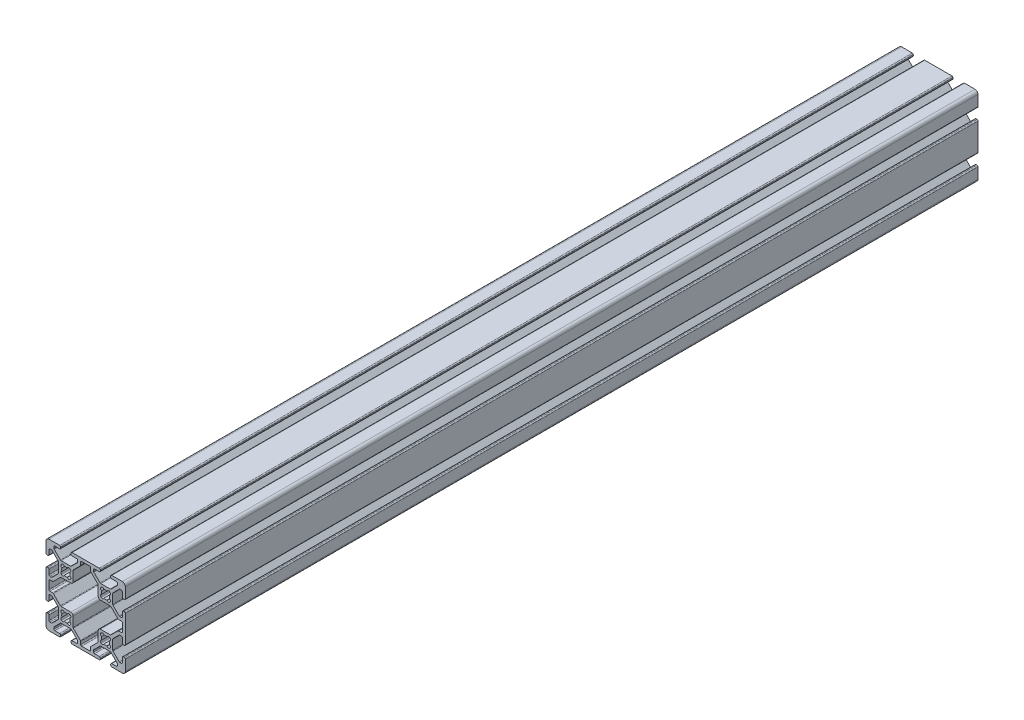
SolidWorks part; units mm, degrees
material "6105-T5 Aluminum"
ref_plane "Front Plane" through (0, 0, 0) normal (0, 0, 1) x (1, 0, 0)
ref_plane "Top Plane" through (0, 0, 0) normal (0, 1, 0) x (1, 0, 0)
ref_plane "Right Plane" through (0, 0, 0) normal (1, 0, 0) x (0, 0, -1)
sketch "Sketch1" plane through (0, 0, 0) normal (0, 0, 1) x (1, 0, 0)
  line L0 (-2.1249, 17.6955) -> (-2.3045, 17.8751)
  line L1 (-2.3045, 22.1249) -> (-2.1249, 22.3045)
  line L2 (2.1249, 22.3045) -> (2.3045, 22.1249)
  line L3 (2.3045, 17.8751) -> (2.1249, 17.6955)
  line L4 (-22.1249, 17.6955) -> (-22.3045, 17.8751)
  line L5 (-22.3045, 22.1249) -> (-22.1249, 22.3045)
  line L6 (-17.8751, 22.3045) -> (-17.6955, 22.1249)
  line L7 (-17.6955, 17.8751) -> (-17.8751, 17.6955)
  line L8 (-2.1249, -2.3045) -> (-2.3045, -2.1249)
  line L9 (-2.3045, 2.1249) -> (-2.1249, 2.3045)
  line L10 (2.1249, 2.3045) -> (2.3045, 2.1249)
  line L11 (2.3045, -2.1249) -> (2.1249, -2.3045)
  line L12 (-12.505, -7.992) -> (-12.505, -6.6448)
  line L13 (-12.6538, -6.2856) -> (-16.1962, -2.7431)
  line L14 (-16.345, -2.3839) -> (-16.345, 2.512)
  line L15 (-17.488, 3.655) -> (-22.3839, 3.655)
  line L16 (-22.7431, 3.8038) -> (-26.2856, 7.3462)
  line L17 (-26.6448, 7.495) -> (-27.992, 7.495)
  line L18 (-28.5, 8.003) -> (-28.5, 11.997)
  line L19 (-27.992, 12.505) -> (-26.6448, 12.505)
  line L20 (-26.2856, 12.6538) -> (-22.7431, 16.1962)
  line L21 (-22.3839, 16.345) -> (-17.488, 16.345)
  line L22 (-16.345, 17.488) -> (-16.345, 22.3839)
  line L23 (-16.1962, 22.7431) -> (-12.6538, 26.2856)
  line L24 (-12.505, 26.6448) -> (-12.505, 27.992)
  line L25 (-11.997, 28.5) -> (-8.003, 28.5)
  line L26 (-7.495, 27.992) -> (-7.495, 26.6448)
  line L27 (-7.3462, 26.2856) -> (-3.8038, 22.7431)
  line L28 (-3.655, 22.3839) -> (-3.655, 17.488)
  line L29 (-2.512, 16.345) -> (2.3839, 16.345)
  line L30 (2.7431, 16.1962) -> (6.2856, 12.6538)
  line L31 (6.6448, 12.505) -> (7.992, 12.505)
  line L32 (8.5, 11.997) -> (8.5, 8.003)
  line L33 (7.992, 7.495) -> (6.6448, 7.495)
  line L34 (6.2856, 7.3462) -> (2.7431, 3.8038)
  line L35 (2.3839, 3.655) -> (-2.512, 3.655)
  line L36 (-3.655, 2.512) -> (-3.655, -2.3839)
  line L37 (-3.8038, -2.7431) -> (-7.3462, -6.2856)
  line L38 (-7.495, -6.6448) -> (-7.495, -7.992)
  line L39 (-8.003, -8.5) -> (-11.997, -8.5)
  line L40 (-22.1249, -2.3045) -> (-22.3045, -2.1249)
  line L41 (-22.3045, 2.1249) -> (-22.1249, 2.3045)
  line L42 (-17.8751, 2.3045) -> (-17.6955, 2.1249)
  line L43 (-17.6955, -2.1249) -> (-17.8751, -2.3045)
  line L44 (-22.3839, -3.655) -> (-17.6161, -3.655)
  line L45 (-17.2569, -3.8038) -> (-14.1538, -6.9069)
  line L46 (-14.005, -7.2661) -> (-14.005, -7.992)
  line L47 (-14.513, -8.5) -> (-16.862, -8.5)
  line L48 (-17.37, -9.008) -> (-17.37, -9.492)
  line L49 (-16.862, -10) -> (-3.138, -10)
  line L50 (-2.63, -9.492) -> (-2.63, -9.008)
  line L51 (-3.138, -8.5) -> (-5.487, -8.5)
  line L52 (-5.995, -7.992) -> (-5.995, -7.2661)
  line L53 (-5.8462, -6.9069) -> (-2.7431, -3.8038)
  line L54 (-2.3839, -3.655) -> (2.3839, -3.655)
  line L55 (2.7431, -3.8038) -> (5.8462, -6.9069)
  line L56 (5.995, -7.2661) -> (5.995, -7.992)
  line L57 (5.487, -8.5) -> (3.138, -8.5)
  line L58 (2.63, -9.008) -> (2.63, -9.492)
  line L59 (3.138, -10) -> (8.5, -10)
  line L60 (10, -8.5) -> (10, -3.138)
  line L61 (9.492, -2.63) -> (9.008, -2.63)
  line L62 (8.5, -3.138) -> (8.5, -5.487)
  line L63 (7.992, -5.995) -> (7.2661, -5.995)
  line L64 (6.9069, -5.8462) -> (3.8038, -2.7431)
  line L65 (3.655, -2.3839) -> (3.655, 2.3839)
  line L66 (3.8038, 2.7431) -> (6.9069, 5.8462)
  line L67 (7.2661, 5.995) -> (7.992, 5.995)
  line L68 (8.5, 5.487) -> (8.5, 3.138)
  line L69 (9.008, 2.63) -> (9.492, 2.63)
  line L70 (10, 3.138) -> (10, 16.862)
  line L71 (9.492, 17.37) -> (9.008, 17.37)
  line L72 (8.5, 16.862) -> (8.5, 14.513)
  line L73 (7.992, 14.005) -> (7.2661, 14.005)
  line L74 (6.9069, 14.1538) -> (3.8038, 17.2569)
  line L75 (3.655, 17.6161) -> (3.655, 22.3839)
  line L76 (3.8038, 22.7431) -> (6.9069, 25.8462)
  line L77 (7.2661, 25.995) -> (7.992, 25.995)
  line L78 (8.5, 25.487) -> (8.5, 23.138)
  line L79 (9.008, 22.63) -> (9.492, 22.63)
  line L80 (10, 23.138) -> (10, 28.5)
  line L81 (8.5, 30) -> (3.138, 30)
  line L82 (2.63, 29.492) -> (2.63, 29.008)
  line L83 (3.138, 28.5) -> (5.487, 28.5)
  line L84 (5.995, 27.992) -> (5.995, 27.2661)
  line L85 (5.8462, 26.9069) -> (2.7431, 23.8038)
  line L86 (2.3839, 23.655) -> (-2.3839, 23.655)
  line L87 (-2.7431, 23.8038) -> (-5.8462, 26.9069)
  line L88 (-5.995, 27.2661) -> (-5.995, 27.992)
  line L89 (-5.487, 28.5) -> (-3.138, 28.5)
  line L90 (-2.63, 29.008) -> (-2.63, 29.492)
  line L91 (-3.138, 30) -> (-16.862, 30)
  line L92 (-17.37, 29.492) -> (-17.37, 29.008)
  line L93 (-16.862, 28.5) -> (-14.513, 28.5)
  line L94 (-14.005, 27.992) -> (-14.005, 27.2661)
  line L95 (-14.1538, 26.9069) -> (-17.2569, 23.8038)
  line L96 (-17.6161, 23.655) -> (-22.3839, 23.655)
  line L97 (-22.7431, 23.8038) -> (-25.8462, 26.9069)
  line L98 (-25.995, 27.2661) -> (-25.995, 27.992)
  line L99 (-25.487, 28.5) -> (-23.138, 28.5)
  line L100 (-22.63, 29.008) -> (-22.63, 29.492)
  line L101 (-23.138, 30) -> (-28.5, 30)
  line L102 (-30, 28.5) -> (-30, 23.138)
  line L103 (-29.492, 22.63) -> (-29.008, 22.63)
  line L104 (-28.5, 23.138) -> (-28.5, 25.487)
  line L105 (-27.992, 25.995) -> (-27.2661, 25.995)
  line L106 (-26.9069, 25.8462) -> (-23.8038, 22.7431)
  line L107 (-23.655, 22.3839) -> (-23.655, 17.6161)
  line L108 (-23.8038, 17.2569) -> (-26.9069, 14.1538)
  line L109 (-27.2661, 14.005) -> (-27.992, 14.005)
  line L110 (-28.5, 14.513) -> (-28.5, 16.862)
  line L111 (-29.008, 17.37) -> (-29.492, 17.37)
  line L112 (-30, 16.862) -> (-30, 3.138)
  line L113 (-29.492, 2.63) -> (-29.008, 2.63)
  line L114 (-28.5, 3.138) -> (-28.5, 5.487)
  line L115 (-27.992, 5.995) -> (-27.2661, 5.995)
  line L116 (-26.9069, 5.8462) -> (-23.8038, 2.7431)
  line L117 (-23.655, 2.3839) -> (-23.655, -2.3839)
  line L118 (-23.8038, -2.7431) -> (-26.9069, -5.8462)
  line L119 (-27.2661, -5.995) -> (-27.992, -5.995)
  line L120 (-28.5, -5.487) -> (-28.5, -3.138)
  line L121 (-29.008, -2.63) -> (-29.492, -2.63)
  line L122 (-30, -3.138) -> (-30, -8.5)
  line L123 (-28.5, -10) -> (-23.138, -10)
  line L124 (-22.63, -9.492) -> (-22.63, -9.008)
  line L125 (-23.138, -8.5) -> (-25.487, -8.5)
  line L126 (-25.995, -7.992) -> (-25.995, -7.2661)
  line L127 (-25.8462, -6.9069) -> (-22.7431, -3.8038)
  arc A0 (-1.9351, 19.196) -> (-2.3045, 17.8751) centre (-1.748, 18.4316) ccw
  arc A1 (-1.9351, 20.804) -> (-1.9351, 19.196) centre (0, 20) ccw
  arc A2 (-2.3045, 22.1249) -> (-1.9351, 20.804) centre (-1.748, 21.5684) ccw
  arc A3 (-0.804, 21.9351) -> (-2.1249, 22.3045) centre (-1.5684, 21.748) ccw
  arc A4 (0.804, 21.9351) -> (-0.804, 21.9351) centre (0, 20) ccw
  arc A5 (2.1249, 22.3045) -> (0.804, 21.9351) centre (1.5684, 21.748) ccw
  arc A6 (1.9351, 20.804) -> (2.3045, 22.1249) centre (1.748, 21.5684) ccw
  arc A7 (1.9351, 19.196) -> (1.9351, 20.804) centre (0, 20) ccw
  arc A8 (2.3045, 17.8751) -> (1.9351, 19.196) centre (1.748, 18.4316) ccw
  arc A9 (0.804, 18.0649) -> (2.1249, 17.6955) centre (1.5684, 18.252) ccw
  arc A10 (-0.804, 18.0649) -> (0.804, 18.0649) centre (0, 20) ccw
  arc A11 (-2.1249, 17.6955) -> (-0.804, 18.0649) centre (-1.5684, 18.252) ccw
  arc A12 (-21.9351, 19.196) -> (-22.3045, 17.8751) centre (-21.748, 18.4316) ccw
  arc A13 (-21.9351, 20.804) -> (-21.9351, 19.196) centre (-20, 20) ccw
  arc A14 (-22.3045, 22.1249) -> (-21.9351, 20.804) centre (-21.748, 21.5684) ccw
  arc A15 (-20.804, 21.9351) -> (-22.1249, 22.3045) centre (-21.5684, 21.748) ccw
  arc A16 (-19.196, 21.9351) -> (-20.804, 21.9351) centre (-20, 20) ccw
  arc A17 (-17.8751, 22.3045) -> (-19.196, 21.9351) centre (-18.4316, 21.748) ccw
  arc A18 (-18.0649, 20.804) -> (-17.6955, 22.1249) centre (-18.252, 21.5684) ccw
  arc A19 (-18.0649, 19.196) -> (-18.0649, 20.804) centre (-20, 20) ccw
  arc A20 (-17.6955, 17.8751) -> (-18.0649, 19.196) centre (-18.252, 18.4316) ccw
  arc A21 (-19.196, 18.0649) -> (-17.8751, 17.6955) centre (-18.4316, 18.252) ccw
  arc A22 (-20.804, 18.0649) -> (-19.196, 18.0649) centre (-20, 20) ccw
  arc A23 (-22.1249, 17.6955) -> (-20.804, 18.0649) centre (-21.5684, 18.252) ccw
  arc A24 (-1.9351, -0.804) -> (-2.3045, -2.1249) centre (-1.748, -1.5684) ccw
  arc A25 (-1.9351, 0.804) -> (-1.9351, -0.804) centre (0, 0) ccw
  arc A26 (-2.3045, 2.1249) -> (-1.9351, 0.804) centre (-1.748, 1.5684) ccw
  arc A27 (-0.804, 1.9351) -> (-2.1249, 2.3045) centre (-1.5684, 1.748) ccw
  arc A28 (0.804, 1.9351) -> (-0.804, 1.9351) centre (0, 0) ccw
  arc A29 (2.1249, 2.3045) -> (0.804, 1.9351) centre (1.5684, 1.748) ccw
  arc A30 (1.9351, 0.804) -> (2.3045, 2.1249) centre (1.748, 1.5684) ccw
  arc A31 (1.9351, -0.804) -> (1.9351, 0.804) centre (0, 0) ccw
  arc A32 (2.3045, -2.1249) -> (1.9351, -0.804) centre (1.748, -1.5684) ccw
  arc A33 (0.804, -1.9351) -> (2.1249, -2.3045) centre (1.5684, -1.748) ccw
  arc A34 (-0.804, -1.9351) -> (0.804, -1.9351) centre (0, 0) ccw
  arc A35 (-2.1249, -2.3045) -> (-0.804, -1.9351) centre (-1.5684, -1.748) ccw
  arc A36 (-12.505, -7.992) -> (-11.997, -8.5) centre (-11.997, -7.992) ccw
  arc A37 (-12.505, -6.6448) -> (-12.6538, -6.2856) centre (-13.013, -6.6448) ccw
  arc A38 (-16.345, -2.3839) -> (-16.1962, -2.7431) centre (-15.837, -2.3839) ccw
  arc A39 (-16.345, 2.512) -> (-17.488, 3.655) centre (-17.488, 2.512) ccw
  arc A40 (-22.7431, 3.8038) -> (-22.3839, 3.655) centre (-22.3839, 4.163) ccw
  arc A41 (-26.2856, 7.3462) -> (-26.6448, 7.495) centre (-26.6448, 6.987) ccw
  arc A42 (-28.5, 8.003) -> (-27.992, 7.495) centre (-27.992, 8.003) ccw
  arc A43 (-27.992, 12.505) -> (-28.5, 11.997) centre (-27.992, 11.997) ccw
  arc A44 (-26.6448, 12.505) -> (-26.2856, 12.6538) centre (-26.6448, 13.013) ccw
  arc A45 (-22.3839, 16.345) -> (-22.7431, 16.1962) centre (-22.3839, 15.837) ccw
  arc A46 (-17.488, 16.345) -> (-16.345, 17.488) centre (-17.488, 17.488) ccw
  arc A47 (-16.1962, 22.7431) -> (-16.345, 22.3839) centre (-15.837, 22.3839) ccw
  arc A48 (-12.6538, 26.2856) -> (-12.505, 26.6448) centre (-13.013, 26.6448) ccw
  arc A49 (-11.997, 28.5) -> (-12.505, 27.992) centre (-11.997, 27.992) ccw
  arc A50 (-7.495, 27.992) -> (-8.003, 28.5) centre (-8.003, 27.992) ccw
  arc A51 (-7.495, 26.6448) -> (-7.3462, 26.2856) centre (-6.987, 26.6448) ccw
  arc A52 (-3.655, 22.3839) -> (-3.8038, 22.7431) centre (-4.163, 22.3839) ccw
  arc A53 (-3.655, 17.488) -> (-2.512, 16.345) centre (-2.512, 17.488) ccw
  arc A54 (2.7431, 16.1962) -> (2.3839, 16.345) centre (2.3839, 15.837) ccw
  arc A55 (6.2856, 12.6538) -> (6.6448, 12.505) centre (6.6448, 13.013) ccw
  arc A56 (8.5, 11.997) -> (7.992, 12.505) centre (7.992, 11.997) ccw
  arc A57 (7.992, 7.495) -> (8.5, 8.003) centre (7.992, 8.003) ccw
  arc A58 (6.6448, 7.495) -> (6.2856, 7.3462) centre (6.6448, 6.987) ccw
  arc A59 (2.3839, 3.655) -> (2.7431, 3.8038) centre (2.3839, 4.163) ccw
  arc A60 (-2.512, 3.655) -> (-3.655, 2.512) centre (-2.512, 2.512) ccw
  arc A61 (-3.8038, -2.7431) -> (-3.655, -2.3839) centre (-4.163, -2.3839) ccw
  arc A62 (-7.3462, -6.2856) -> (-7.495, -6.6448) centre (-6.987, -6.6448) ccw
  arc A63 (-8.003, -8.5) -> (-7.495, -7.992) centre (-8.003, -7.992) ccw
  arc A64 (-21.9351, -0.804) -> (-22.3045, -2.1249) centre (-21.748, -1.5684) ccw
  arc A65 (-21.9351, 0.804) -> (-21.9351, -0.804) centre (-20, 0) ccw
  arc A66 (-22.3045, 2.1249) -> (-21.9351, 0.804) centre (-21.748, 1.5684) ccw
  arc A67 (-20.804, 1.9351) -> (-22.1249, 2.3045) centre (-21.5684, 1.748) ccw
  arc A68 (-19.196, 1.9351) -> (-20.804, 1.9351) centre (-20, 0) ccw
  arc A69 (-17.8751, 2.3045) -> (-19.196, 1.9351) centre (-18.4316, 1.748) ccw
  arc A70 (-18.0649, 0.804) -> (-17.6955, 2.1249) centre (-18.252, 1.5684) ccw
  arc A71 (-18.0649, -0.804) -> (-18.0649, 0.804) centre (-20, 0) ccw
  arc A72 (-17.6955, -2.1249) -> (-18.0649, -0.804) centre (-18.252, -1.5684) ccw
  arc A73 (-19.196, -1.9351) -> (-17.8751, -2.3045) centre (-18.4316, -1.748) ccw
  arc A74 (-20.804, -1.9351) -> (-19.196, -1.9351) centre (-20, 0) ccw
  arc A75 (-22.1249, -2.3045) -> (-20.804, -1.9351) centre (-21.5684, -1.748) ccw
  arc A76 (-22.3839, -3.655) -> (-22.7431, -3.8038) centre (-22.3839, -4.163) ccw
  arc A77 (-17.2569, -3.8038) -> (-17.6161, -3.655) centre (-17.6161, -4.163) ccw
  arc A78 (-14.005, -7.2661) -> (-14.1538, -6.9069) centre (-14.513, -7.2661) ccw
  arc A79 (-14.513, -8.5) -> (-14.005, -7.992) centre (-14.513, -7.992) ccw
  arc A80 (-16.862, -8.5) -> (-17.37, -9.008) centre (-16.862, -9.008) ccw
  arc A81 (-17.37, -9.492) -> (-16.862, -10) centre (-16.862, -9.492) ccw
  arc A82 (-3.138, -10) -> (-2.63, -9.492) centre (-3.138, -9.492) ccw
  arc A83 (-2.63, -9.008) -> (-3.138, -8.5) centre (-3.138, -9.008) ccw
  arc A84 (-5.995, -7.992) -> (-5.487, -8.5) centre (-5.487, -7.992) ccw
  arc A85 (-5.8462, -6.9069) -> (-5.995, -7.2661) centre (-5.487, -7.2661) ccw
  arc A86 (-2.3839, -3.655) -> (-2.7431, -3.8038) centre (-2.3839, -4.163) ccw
  arc A87 (2.7431, -3.8038) -> (2.3839, -3.655) centre (2.3839, -4.163) ccw
  arc A88 (5.995, -7.2661) -> (5.8462, -6.9069) centre (5.487, -7.2661) ccw
  arc A89 (5.487, -8.5) -> (5.995, -7.992) centre (5.487, -7.992) ccw
  arc A90 (3.138, -8.5) -> (2.63, -9.008) centre (3.138, -9.008) ccw
  arc A91 (2.63, -9.492) -> (3.138, -10) centre (3.138, -9.492) ccw
  arc A92 (8.5, -10) -> (10, -8.5) centre (8.5, -8.5) ccw
  arc A93 (10, -3.138) -> (9.492, -2.63) centre (9.492, -3.138) ccw
  arc A94 (9.008, -2.63) -> (8.5, -3.138) centre (9.008, -3.138) ccw
  arc A95 (7.992, -5.995) -> (8.5, -5.487) centre (7.992, -5.487) ccw
  arc A96 (6.9069, -5.8462) -> (7.2661, -5.995) centre (7.2661, -5.487) ccw
  arc A97 (3.655, -2.3839) -> (3.8038, -2.7431) centre (4.163, -2.3839) ccw
  arc A98 (3.8038, 2.7431) -> (3.655, 2.3839) centre (4.163, 2.3839) ccw
  arc A99 (7.2661, 5.995) -> (6.9069, 5.8462) centre (7.2661, 5.487) ccw
  arc A100 (8.5, 5.487) -> (7.992, 5.995) centre (7.992, 5.487) ccw
  arc A101 (8.5, 3.138) -> (9.008, 2.63) centre (9.008, 3.138) ccw
  arc A102 (9.492, 2.63) -> (10, 3.138) centre (9.492, 3.138) ccw
  arc A103 (10, 16.862) -> (9.492, 17.37) centre (9.492, 16.862) ccw
  arc A104 (9.008, 17.37) -> (8.5, 16.862) centre (9.008, 16.862) ccw
  arc A105 (7.992, 14.005) -> (8.5, 14.513) centre (7.992, 14.513) ccw
  arc A106 (6.9069, 14.1538) -> (7.2661, 14.005) centre (7.2661, 14.513) ccw
  arc A107 (3.655, 17.6161) -> (3.8038, 17.2569) centre (4.163, 17.6161) ccw
  arc A108 (3.8038, 22.7431) -> (3.655, 22.3839) centre (4.163, 22.3839) ccw
  arc A109 (7.2661, 25.995) -> (6.9069, 25.8462) centre (7.2661, 25.487) ccw
  arc A110 (8.5, 25.487) -> (7.992, 25.995) centre (7.992, 25.487) ccw
  arc A111 (8.5, 23.138) -> (9.008, 22.63) centre (9.008, 23.138) ccw
  arc A112 (9.492, 22.63) -> (10, 23.138) centre (9.492, 23.138) ccw
  arc A113 (10, 28.5) -> (8.5, 30) centre (8.5, 28.5) ccw
  arc A114 (3.138, 30) -> (2.63, 29.492) centre (3.138, 29.492) ccw
  arc A115 (2.63, 29.008) -> (3.138, 28.5) centre (3.138, 29.008) ccw
  arc A116 (5.995, 27.992) -> (5.487, 28.5) centre (5.487, 27.992) ccw
  arc A117 (5.8462, 26.9069) -> (5.995, 27.2661) centre (5.487, 27.2661) ccw
  arc A118 (2.3839, 23.655) -> (2.7431, 23.8038) centre (2.3839, 24.163) ccw
  arc A119 (-2.7431, 23.8038) -> (-2.3839, 23.655) centre (-2.3839, 24.163) ccw
  arc A120 (-5.995, 27.2661) -> (-5.8462, 26.9069) centre (-5.487, 27.2661) ccw
  arc A121 (-5.487, 28.5) -> (-5.995, 27.992) centre (-5.487, 27.992) ccw
  arc A122 (-3.138, 28.5) -> (-2.63, 29.008) centre (-3.138, 29.008) ccw
  arc A123 (-2.63, 29.492) -> (-3.138, 30) centre (-3.138, 29.492) ccw
  arc A124 (-16.862, 30) -> (-17.37, 29.492) centre (-16.862, 29.492) ccw
  arc A125 (-17.37, 29.008) -> (-16.862, 28.5) centre (-16.862, 29.008) ccw
  arc A126 (-14.005, 27.992) -> (-14.513, 28.5) centre (-14.513, 27.992) ccw
  arc A127 (-14.1538, 26.9069) -> (-14.005, 27.2661) centre (-14.513, 27.2661) ccw
  arc A128 (-17.6161, 23.655) -> (-17.2569, 23.8038) centre (-17.6161, 24.163) ccw
  arc A129 (-22.7431, 23.8038) -> (-22.3839, 23.655) centre (-22.3839, 24.163) ccw
  arc A130 (-25.995, 27.2661) -> (-25.8462, 26.9069) centre (-25.487, 27.2661) ccw
  arc A131 (-25.487, 28.5) -> (-25.995, 27.992) centre (-25.487, 27.992) ccw
  arc A132 (-23.138, 28.5) -> (-22.63, 29.008) centre (-23.138, 29.008) ccw
  arc A133 (-22.63, 29.492) -> (-23.138, 30) centre (-23.138, 29.492) ccw
  arc A134 (-28.5, 30) -> (-30, 28.5) centre (-28.5, 28.5) ccw
  arc A135 (-30, 23.138) -> (-29.492, 22.63) centre (-29.492, 23.138) ccw
  arc A136 (-29.008, 22.63) -> (-28.5, 23.138) centre (-29.008, 23.138) ccw
  arc A137 (-27.992, 25.995) -> (-28.5, 25.487) centre (-27.992, 25.487) ccw
  arc A138 (-26.9069, 25.8462) -> (-27.2661, 25.995) centre (-27.2661, 25.487) ccw
  arc A139 (-23.655, 22.3839) -> (-23.8038, 22.7431) centre (-24.163, 22.3839) ccw
  arc A140 (-23.8038, 17.2569) -> (-23.655, 17.6161) centre (-24.163, 17.6161) ccw
  arc A141 (-27.2661, 14.005) -> (-26.9069, 14.1538) centre (-27.2661, 14.513) ccw
  arc A142 (-28.5, 14.513) -> (-27.992, 14.005) centre (-27.992, 14.513) ccw
  arc A143 (-28.5, 16.862) -> (-29.008, 17.37) centre (-29.008, 16.862) ccw
  arc A144 (-29.492, 17.37) -> (-30, 16.862) centre (-29.492, 16.862) ccw
  arc A145 (-30, 3.138) -> (-29.492, 2.63) centre (-29.492, 3.138) ccw
  arc A146 (-29.008, 2.63) -> (-28.5, 3.138) centre (-29.008, 3.138) ccw
  arc A147 (-27.992, 5.995) -> (-28.5, 5.487) centre (-27.992, 5.487) ccw
  arc A148 (-26.9069, 5.8462) -> (-27.2661, 5.995) centre (-27.2661, 5.487) ccw
  arc A149 (-23.655, 2.3839) -> (-23.8038, 2.7431) centre (-24.163, 2.3839) ccw
  arc A150 (-23.8038, -2.7431) -> (-23.655, -2.3839) centre (-24.163, -2.3839) ccw
  arc A151 (-27.2661, -5.995) -> (-26.9069, -5.8462) centre (-27.2661, -5.487) ccw
  arc A152 (-28.5, -5.487) -> (-27.992, -5.995) centre (-27.992, -5.487) ccw
  arc A153 (-28.5, -3.138) -> (-29.008, -2.63) centre (-29.008, -3.138) ccw
  arc A154 (-29.492, -2.63) -> (-30, -3.138) centre (-29.492, -3.138) ccw
  arc A155 (-30, -8.5) -> (-28.5, -10) centre (-28.5, -8.5) ccw
  arc A156 (-23.138, -10) -> (-22.63, -9.492) centre (-23.138, -9.492) ccw
  arc A157 (-22.63, -9.008) -> (-23.138, -8.5) centre (-23.138, -9.008) ccw
  arc A158 (-25.995, -7.992) -> (-25.487, -8.5) centre (-25.487, -7.992) ccw
  arc A159 (-25.8462, -6.9069) -> (-25.995, -7.2661) centre (-25.487, -7.2661) ccw
extrude "Extrude1" add sketch "Sketch1" against normal blind 430
